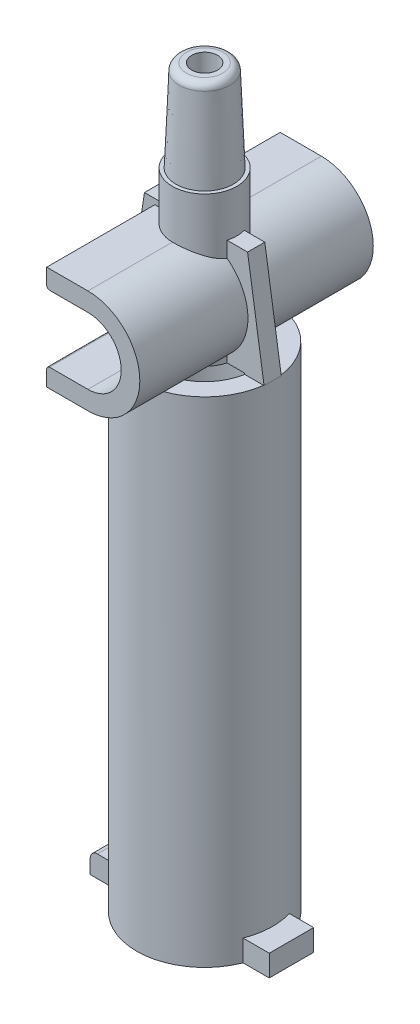
SolidWorks part; units mm, degrees
ref_plane "Front Plane" through (0, 0, 0) normal (0, 0, 1) x (1, 0, 0)
ref_plane "Top Plane" through (0, 0, 0) normal (0, 1, 0) x (1, 0, 0)
ref_plane "Right Plane" through (0, 0, 0) normal (1, 0, 0) x (0, 0, -1)
sketch "Sketch1" plane through (0, 0, 0) normal (0, 1, 0) x (1, 0, 0)
  circle A0 centre (0, 0) radius 4.75
  dimension "D1" = 9.5
extrude "Boss-Extrude1" add sketch "Sketch1" along normal blind 34.5
sketch "Sketch2" plane through (0, 0, 0) normal (0, 0, 1) x (1, 0, 0)
  line L0 (-4.75, 34.5) -> (-3.6, 42)
  line L1 (-3.6, 42) -> (3.6, 42)
  line L2 (3.6, 42) -> (4.75, 34.5)
  line L3 (4.75, 34.5) -> (-4.75, 34.5) construction
  line L4 (0, 0) -> (0, 10.0336) construction
  line L5 (-4.75, 34.5) -> (4.75, 34.5)
  dimension "D1" = 7.2
  dimension "D2" = 7.5
extrude "Boss-Extrude3" add sketch "Sketch2" along normal blind 0.6 and the other way blind 0.6
sketch "Sketch6" plane through (0, 0, 0.6) normal (0, 0, 1) x (1, 0, 0)
  line L0 (-4.75, 0) -> (4.75, 0) construction
  line L1 (0, 41.625) -> (-2.875, 41.625)
  line L2 (-2.875, 41.625) -> (-2.875, 34.375)
  line L3 (-2.875, 34.375) -> (0, 34.375)
  arc A0 (0, 34.375) -> (0, 41.625) centre (0, 38) ccw
  dimension "D1" = 7.25
  dimension "D2" = 38
extrude "Boss-Extrude6" add sketch "Sketch6" along normal blind 7.55
sketch "Sketch9" plane through (0, 0, 8.15) normal (0, 0, 1) x (1, 0, 0)
  line L0 (-2.875, 40.325) -> (0, 40.325)
  line L1 (-2.875, 41.625) -> (-2.875, 34.5) construction
  line L2 (0, 35.675) -> (-2.875, 35.675)
  line L3 (-2.875, 35.675) -> (-2.875, 40.325)
  line L4 (0, 41.625) -> (-2.875, 41.625) construction
  line L5 (-2.875, 34.375) -> (0, 34.375) construction
  arc A0 (0, 40.325) -> (0, 35.675) centre (0, 38) cw
  arc A1 (0, 34.375) -> (0, 41.625) centre (0, 38) ccw construction
  arc A2 (0.9437, 34.5) -> (0, 41.625) centre (0, 38) ccw construction
  dimension "D1" = 1.3
extrude "Cut-Extrude2" cut sketch "Sketch9" against normal blind 7.55
fillet "Fillet2" radius 0.2 2 edges at (-2.875, 35.675, 4.375) (-2.875, 40.325, 4.375)
mirror "Mirror1" about plane through (0, 0, 0) normal (0, 0, 1) of "Cut-Extrude2", "Boss-Extrude6", "Fillet2"
sketch "Sketch10" plane through (0, 34.5, 0) normal (0, 1, 0) x (1, 0, 0)
  circle A0 centre (0, 0) radius 2.25
  dimension "D1" = 4.5
extrude "Boss-Extrude7" add sketch "Sketch10" along normal blind 10.5
ref_plane "Plane1" through (0, 51.35, 0) normal (0, 1, 0) x (1, 0, 0)
sketch "Sketch11" plane through (0, 45, 0) normal (0, 1, 0) x (1, 0, 0)
  circle A0 centre (0, 0) radius 2
  dimension "D1" = 4
sketch "Sketch13" plane through (0, 51.35, 0) normal (0, 1, 0) x (1, 0, 0)
  circle A0 centre (0, 0) radius 1.75
  dimension "D1" = 3.5
loft "Loft1" add profiles "Sketch11", "Sketch13" connector at (1.7291, 45, -1.0051) connector at (1.4881, 51.35, -0.9209)
sketch "Sketch14" plane through (0, 0, 0) normal (1, 0, 0) x (0, 0, -1)
  line L0 (-4.75, 0) -> (4.75, 0) construction
  line L1 (-1.7375, 0) -> (1.3625, 0)
  line L2 (-1.7375, 0) -> (-1.7375, 1.5)
  line L3 (-1.7375, 1.5) -> (1.3625, 1.5)
  line L4 (1.3625, 0) -> (1.3625, 1.5)
  line L5 (-0.1875, 0) -> (-0.1875, 2.775) construction
  dimension "D1" = 3.1
  dimension "D2" = 1.5
extrude "Boss-Extrude8" add sketch "Sketch14" along normal blind 6.25 and the other way blind 6.25
sketch "Sketch15" plane through (0, 0, 0) normal (0, -1, 0) x (1, 0, 0)
  circle A0 centre (0, 0) radius 3.45
  arc A1 (4.4208, 1.7375) -> (-4.4208, 1.7375) centre (0, 0) ccw construction
  dimension "D1" = 1.3
extrude "Cut-Extrude3" cut sketch "Sketch15" against normal blind 34.58
fillet "Fillet3" radius 0.2 1 edges at (0, 0, -3.45)
sketch "Sketch16" plane through (0, 51.35, 0) normal (0, 1, 0) x (1, 0, 0)
  circle A0 centre (0, 0) radius 0.9
  dimension "D1" = 1.8
extrude "Cut-Extrude4" cut sketch "Sketch16" against normal blind 34.58
fillet "Fillet4" radius 0.5 2 edges at (0, 51.35, 1.75) (-6.25, 1.5, 0.1875)
